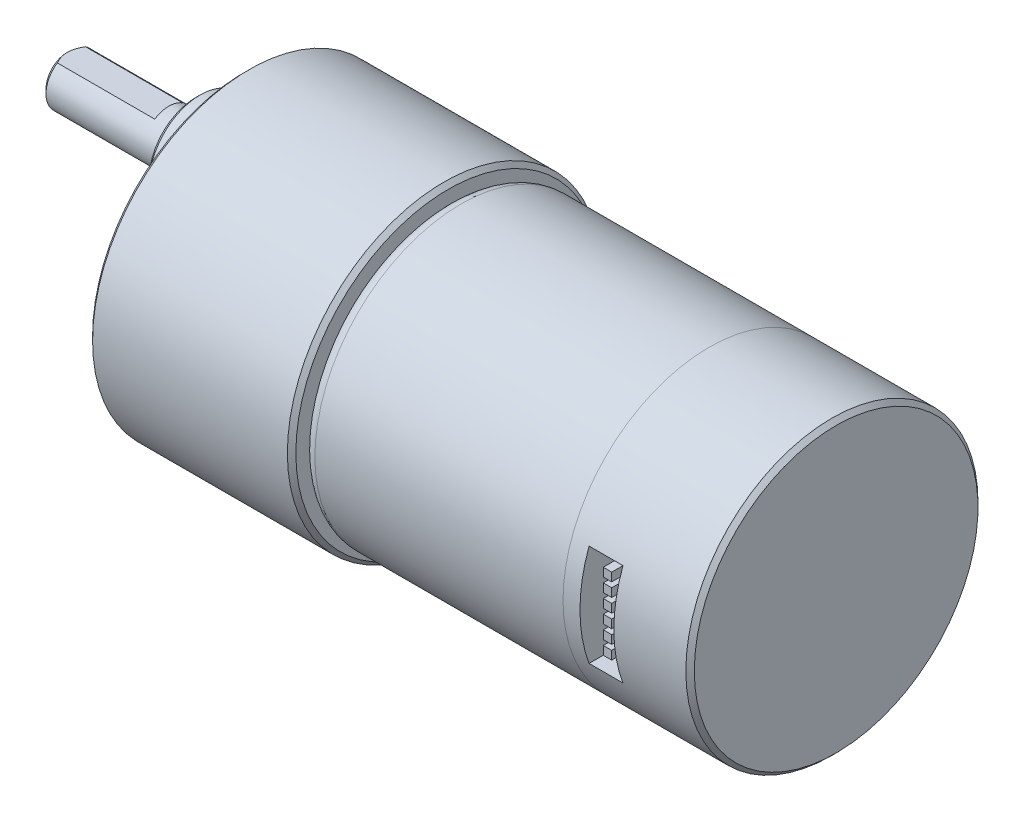
SolidWorks part; units mm, degrees
ref_plane "Front Plane" through (0, 0, 0) normal (0, 0, 1) x (1, 0, 0)
ref_plane "Top Plane" through (0, 0, 0) normal (0, 1, 0) x (1, 0, 0)
ref_plane "Right Plane" through (0, 0, 0) normal (1, 0, 0) x (0, 0, -1)
sketch "Sketch1" plane through (0, 0, 0) normal (0, 1, 0) x (1, 0, 0)
  line L0 (0, 0) -> (69.8, 0)
  line L1 (0, 0) -> (0, 18.5)
  line L2 (0, 18.5) -> (24, 18.5)
  line L3 (24, 18.5) -> (24, 15.75)
  line L4 (25.5, 17.25) -> (69.8, 17.25)
  line L5 (69.8, 17.25) -> (69.8, 0)
  arc A0 (24, 15.75) -> (25.5, 17.25) centre (25.5, 15.75) cw
  dimension "D5" = 1.5
  dimension "D1" = 69.8
  dimension "D2" = 18.5
  dimension "D3" = 24
  dimension "D4" = 17.25
revolve "Revolve1" add sketch "Sketch1" angle 360 about L0
sketch "Sketch3" plane through (0, 0, 0) normal (-1, 0, 0) x (0, 0, 1)
  circle A0 centre (0, 7) radius 6
  dimension "D1" = 12
  dimension "D2" = 7
extrude "Boss-Extrude1" add sketch "Sketch3" along normal blind 5.8
sketch "Sketch4" plane through (-5.8, 0, 0) normal (-1, 0, 0) x (0, 0, 1)
  circle A1 centre (0, 7) radius 3
  dimension "D1" = 6
extrude "Boss-Extrude2" add sketch "Sketch4" along normal blind 15.2
sketch "Sketch5" plane through (-21, 0, 0) normal (-1, 0, 0) x (0, 0, 1)
  line L0 (-1.6583, 9.5) -> (1.6583, 9.5)
  line L1 (1.6583, 9.5) -> (1.6583, 11.6731)
  line L2 (1.6583, 11.6731) -> (-1.6583, 11.6731)
  line L3 (-1.6583, 11.6731) -> (-1.6583, 9.5)
  circle A0 centre (0, 7) radius 3 construction
  circle A1 centre (0, 7) radius 3 construction
  dimension "D1" = 2.5
  dimension "D2" = 2.1731
extrude "Cut-Extrude1" cut sketch "Sketch5" against normal blind 12
chamfer "Chamfer1" distance 0.5 angle 45 5 edges at (69.8, 0, 17.25) (-5.8, 7, 6) (0, 0, 18.5) (-21, 4, 0) (24, 0, 18.5)
sketch "Sketch6" plane through (0, 0, 0) normal (-1, 0, 0) x (0, 0, 1)
  arc A0 (-8.8025, 8.875) -> (8.8025, 8.875) centre (0, 0) ccw
  arc A1 (-8.8025, 8.875) -> (8.8025, 8.875) centre (0, 7) ccw
  dimension "D1" = 25
  dimension "D2" = 18
extrude "Cut-Extrude2" cut sketch "Sketch6" against normal blind 1
sketch "Sketch7" plane through (0, 0, 0) normal (-1, 0, 0) x (0, 0, 1)
  line L0 (-7.75, -13.4234) -> (0, 0) construction
  line L1 (0, 0) -> (-7.75, 13.4234) construction
  line L2 (-7.75, 13.4234) -> (15.5, 0) construction
  line L3 (15.5, 0) -> (0, 0) construction
  circle A0 centre (-7.75, -13.4234) radius 1.5 construction
  circle A1 centre (-7.75, 13.4234) radius 1.5 construction
  circle A2 centre (15.5, 0) radius 1.5 construction
  circle A3 centre (0, 0) radius 15.5 construction
  dimension "D3" = 3
  dimension "D4" = 31
  dimension "D1" = 120
  dimension "D2" = 120
hole_wizard "M3 Tapped Hole1" positions "3DSketch1" profile "Sketch8" tap size "M3" standard "ISO"
sketch3d "3DSketch1"
  point P0 (0, -13.4234, -7.75)
  point P3 (0, 13.4234, -7.75)
  point P6 (0, 0, 15.5)
sketch "Sketch8" plane through (0, -13.4234, -7.75) normal (0, 1, 0) x (0, 0, 1)
  line L0 (0, 0) -> (0, 4.7511)
  line L1 (0, 4.7511) -> (1.25, 4)
  line L2 (1.25, 4) -> (1.25, 0)
  line L5 (1.25, 0) -> (0, 0)
  line L10 (0, 4.7511) -> (-1.25, 4) construction
  line L11 (0, -6.35) -> (0, 107.95) construction
  dimension "Tap Drill Dia." = 2.5
  dimension "Tap Drill Depth" = 4
  dimension "Drill Angle" = 118
cosmetic thread "Hole Thread1" parameters "D1"=3.5, "D2"=3
cosmetic thread "Hole Thread2" parameters "D1"=3.5, "D2"=3
cosmetic thread "Hole Thread3" parameters "D1"=3.5, "D2"=3
pattern_circular "CirPattern1" count 2 over 360 about axis through (0, 0, 0) along (-1, 0, 0) of "M3 Tapped Hole1"
ref_plane "Plane1" through (0, 0, 40) normal (0, 0, 1) x (1, 0, 0)
sketch "Sketch9" plane through (0, 0, 40) normal (0, 0, 1) x (1, 0, 0)
  line L0 (54.8, -31.9517) -> (54.8, 33.9369)
  line L1 (69.8, -16.75) -> (69.8, 16.75) construction
  dimension "D1" = 15
split line "Split Line1"
sketch "Sketch10" plane through (0, 0, 40) normal (0, 0, 1) x (1, 0, 0)
  line L0 (54.8, -17.25) -> (54.8, 17.25) construction
  line L1 (56.8, -6) -> (60.8, -6)
  line L2 (56.8, -6) -> (56.8, 6)
  line L3 (56.8, 6) -> (60.8, 6)
  line L4 (60.8, -6) -> (60.8, 6)
  line L5 (56.8, -6) -> (60.8, 6) construction
  line L6 (56.8, 6) -> (60.8, -6) construction
  point P0 (58.8, 0)
  dimension "D1" = 12
  dimension "D2" = 4
  dimension "D3" = 2
extrude "Cut-Extrude3" cut sketch "Sketch10" against normal blind 28
sketch "Sketch11" plane through (0, 0, 12) normal (0, 0, 1) x (1, 0, 0)
  line L0 (60.8, -6) -> (60.8, 6) construction
  line L1 (58.3, -3.5) -> (59.3, -3.5)
  line L2 (58.3, -3.5) -> (58.3, -4.5)
  line L3 (58.3, -4.5) -> (59.3, -4.5)
  line L4 (59.3, -3.5) -> (59.3, -4.5)
  line L5 (58.3, -3.5) -> (59.3, -4.5) construction
  line L6 (58.3, -4.5) -> (59.3, -3.5) construction
  line L7 (56.8, -6) -> (60.8, -6) construction
  point P0 (58.8, -4)
  dimension "D1" = 1
  dimension "D2" = 1
  dimension "D3" = 2
  dimension "D4" = 2
extrude "Boss-Extrude3" add sketch "Sketch11" along normal blind 4
pattern_linear "LPattern1" count 6 spacing 1.6 along (0, 1, 0) of "Boss-Extrude3"
